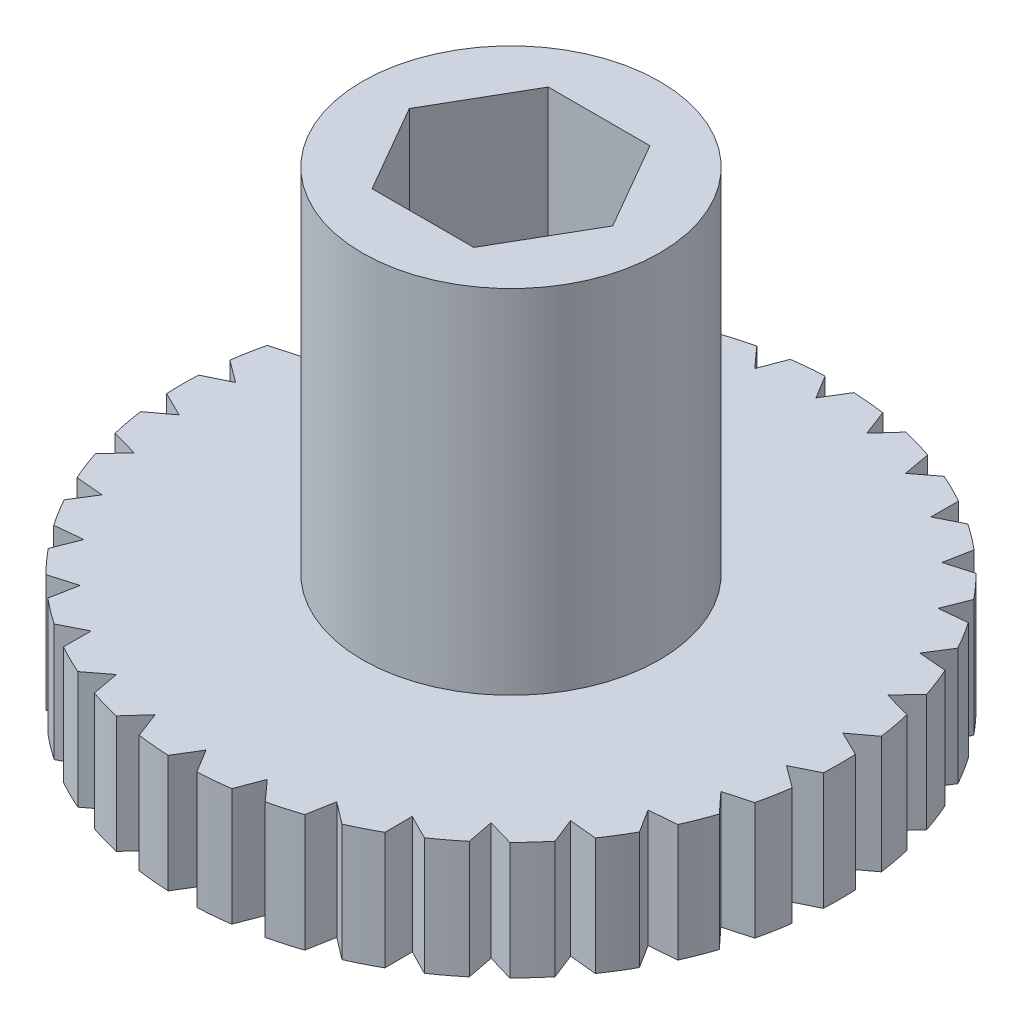
SolidWorks part; units mm, degrees
ref_plane "Front Plane" through (0, 0, 0) normal (0, 0, 1) x (1, 0, 0)
ref_plane "Top Plane" through (0, 0, 0) normal (0, 1, 0) x (1, 0, 0)
ref_plane "Right Plane" through (0, 0, 0) normal (1, 0, 0) x (0, 0, -1)
sketch "Sketch1" plane through (0, 0, 0) normal (0, 1, 0) x (1, 0, 0)
  circle A0 centre (0, 0) radius 14
  dimension "D1" = 28
extrude "Boss-Extrude1" add sketch "Sketch1" against normal blind 5
sketch "Sketch3" plane through (0, 0, 0) normal (0, 1, 0) x (1, 0, 0)
  line L0 (-2.75, 0) -> (2.75, 0) construction
  line L1 (4.3301, 0) -> (2.1651, 3.75)
  line L2 (2.1651, 3.75) -> (-2.1651, 3.75)
  line L3 (-2.1651, 3.75) -> (-4.3301, 0)
  line L4 (-4.3301, 0) -> (-2.1651, -3.75)
  line L5 (-2.1651, -3.75) -> (2.1651, -3.75)
  line L6 (2.1651, -3.75) -> (4.3301, 0)
  circle A0 centre (0, 0) radius 3.75 construction
  point P1 (0, 3.75)
  dimension "D1" = 7.5
extrude "Cut-Extrude1" cut sketch "Sketch3" against normal through all both and the other way through all
sketch "Sketch4" plane through (0, 0, 0) normal (0, 1, 0) x (1, 0, 0)
  line L1 (4.3301, 0) -> (2.1651, 3.75)
  line L2 (2.1651, 3.75) -> (-2.1651, 3.75)
  line L3 (-2.1651, 3.75) -> (-4.3301, 0)
  line L4 (-4.3301, 0) -> (-2.1651, -3.75)
  line L5 (-2.1651, -3.75) -> (2.1651, -3.75)
  line L6 (2.1651, -3.75) -> (4.3301, 0)
  circle A0 centre (0, 0) radius 6.3301
  circle A1 centre (0, 0) radius 4.3301 construction
  circle A2 centre (0, 0) radius 3.75 construction
  dimension "D1" = 2
extrude "Boss-Extrude3" add sketch "Sketch4" along normal blind 15
ref_axis "Axis1" through (0, 0, 0) along (0, -1, 0)
sketch "Sketch6" plane through (0, -5, 0) normal (0, -1, 0) x (1, 0, 0)
  line L0 (0, 0) -> (0, -14) construction
  line L1 (0, 0) -> (-0.6107, -13.9867) construction
  line L2 (0, 0) -> (0.6107, -13.9867) construction
  line L3 (0.6107, -13.9867) -> (-0.6107, -13.9867) construction
  line L4 (0.6107, -13.9867) -> (0, -12.9867)
  line L5 (0, -12.9867) -> (-0.6107, -13.9867)
  circle A0 centre (0, 0) radius 14 construction
  arc A1 (0.6107, -13.9867) -> (-0.6107, -13.9867) centre (0, 0) cw
  point P5 (0, -13.9867)
  dimension "D1" = 5
  dimension "D2" = 1
extrude "Cut-Extrude6" cut sketch "Sketch6" against normal blind 10
pattern_circular "CirPattern1" count 34 over 360 about axis through (0, 0, 0) along (0, -1, 0) of "Cut-Extrude6"
